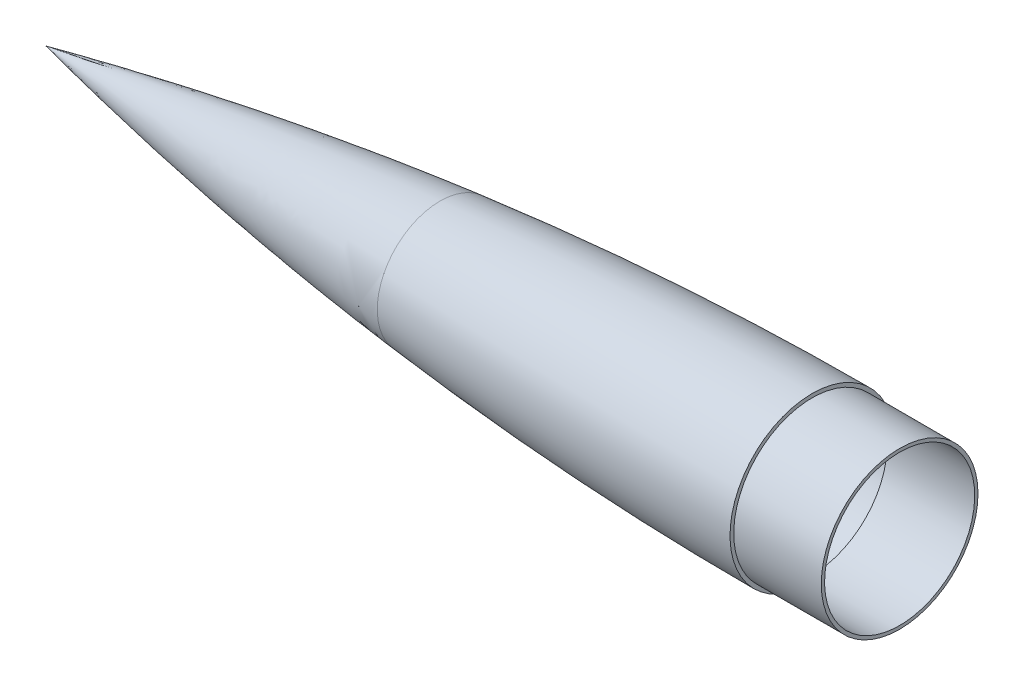
SolidWorks part; units mm, degrees
ref_plane "Plano frontal" through (0, 0, 0) normal (0, 0, 1) x (1, 0, 0)
ref_plane "Plano superior" through (0, 0, 0) normal (0, 1, 0) x (1, 0, 0)
ref_plane "Plano direito" through (0, 0, 0) normal (1, 0, 0) x (0, 0, -1)
sketch "Esboço1" plane through (0, 0, 0) normal (0, 0, 1) x (1, 0, 0)
  line L0 (350, 37.5) -> (350, 0)
  line L1 (350, 0) -> (0, 0)
  spline S0 degree 2 poles (-34.4385, -7.7428) (175.2807, 41.619) (385, 37.125) knots 0 0 0 1 1 1 construction
  spline S1 degree 2 poles (0, 0) (175, 37.5) (350, 37.5) knots 0.082106 0.082106 0.082106 0.916555 0.916555 0.916555
revolve "Revolução1" add sketch "Esboço1" angle 360 about L1
shell "Casca1" thickness 2.5 removed face at (350, 37.5, 0)
sketch "Esboço3" plane through (350, 0, 0) normal (1, 0, 0) x (0, 0, -1)
  circle A0 centre (0, 0) radius 35.8
  circle A1 centre (0, 0) radius 34.3
  dimension "D1" = 71.6
  dimension "D2" = 68.6
extrude "Ressalto-extrusão1" add sketch "Esboço3" along normal blind 40
ref_plane "Plano1" through (180, 0, 0) normal (1, 0, 0) x (0, 0, -1)
sketch "Esboço4" plane through (180, 0, 0) normal (1, 0, 0) x (0, 0, -1)
  circle A0 centre (0, 0) radius 26.1395
  circle A1 centre (0, 0) radius 25.14
  dimension "D1" = 52.2791
  dimension "D2" = 50.28
split "Dividir2" trim tools "Plano1" bodies to split 102 resulting bodies 108 109
sketch "Esboço5" plane through (180, 0, 0) normal (1, 0, 0) x (0, 0, -1)
  circle A0 centre (0, 0) radius 26.1395
  circle A1 centre (0, 0) radius 25.14
  dimension "D1" = 52.2791
  dimension "D2" = 50.28
extrude "Ressalto-extrusão3" add sketch "Esboço5" along normal blind 10 and the other way blind 1 separate body
